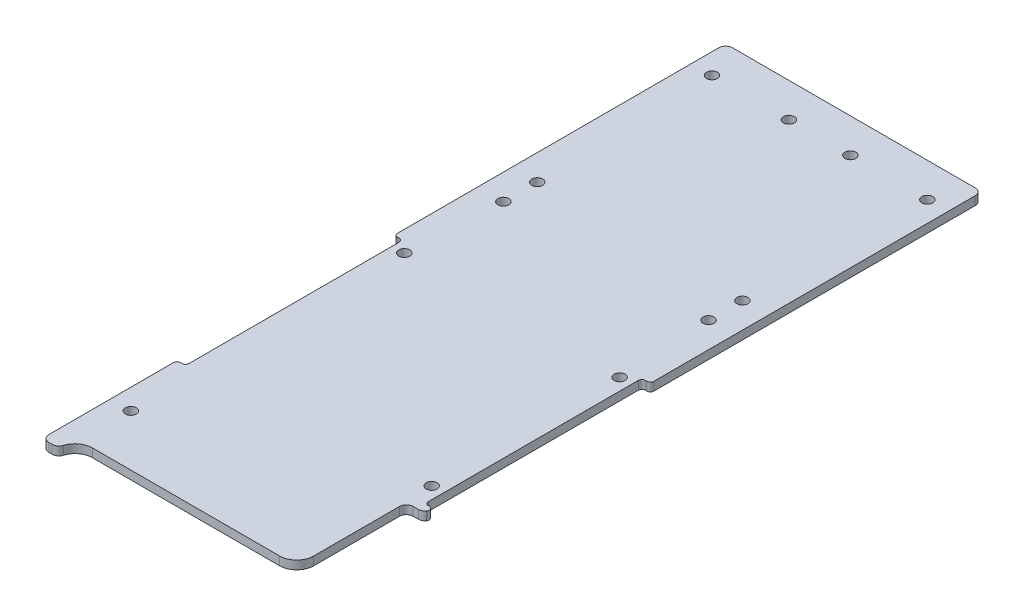
SolidWorks part; units mm, degrees
ref_plane "Front Plane" through (0, 0, 0) normal (0, 0, 1) x (1, 0, 0)
ref_plane "Top Plane" through (0, 0, 0) normal (0, 1, 0) x (1, 0, 0)
ref_plane "Right Plane" through (0, 0, 0) normal (1, 0, 0) x (0, 0, -1)
sketch "Sketch1" plane through (0, 0, 0) normal (0, 1, 0) x (1, 0, 0)
  line L0 (-39.9997, 0) -> (-39.9997, 114.3) construction
  line L1 (-47.625, 127) -> (47.625, 127)
  line L2 (-47.625, 127) -> (-47.625, -127)
  line L3 (-47.625, -127) -> (47.625, -127)
  line L4 (47.625, 127) -> (47.625, -127)
  line L5 (-47.625, 127) -> (47.625, -127) construction
  line L6 (-47.625, -127) -> (47.625, 127) construction
  line L7 (0, 0) -> (0, 127) construction
  line L8 (-39.9997, 0) -> (-39.9997, -101.6) construction
  line L9 (-39.9997, 0) -> (0, 0) construction
  line L10 (-41.275, -127) -> (-41.275, -120.65)
  line L11 (-41.275, -120.65) -> (41.275, -120.65)
  line L12 (41.275, -120.65) -> (41.275, -127)
  line L13 (-39.9997, 114.3) -> (-11.4247, 114.3) construction
  line L14 (39.9997, 114.3) -> (11.4247, 114.3) construction
  circle A0 centre (-39.9997, 114.3) radius 2.032
  circle A1 centre (-39.9997, 0) radius 2.032
  circle A2 centre (-39.9997, -101.6) radius 2.032
  circle A3 centre (39.9997, -101.6) radius 2.032
  circle A4 centre (39.9997, 0) radius 2.032
  circle A5 centre (39.9997, 114.3) radius 2.032
  circle A6 centre (-11.4247, 114.3) radius 2.032
  circle A7 centre (11.4247, 114.3) radius 2.032
  circle A8 centre (-39.9997, -69.85) radius 2.032
  circle A9 centre (39.9997, -69.85) radius 2.032
  point P0 (0, 0)
  dimension "D4" = 4.064
  dimension "D10" = 28.575
  dimension "D1" = 95.25
  dimension "D2" = 254
  dimension "D3" = 7.6253
  dimension "D5" = 12.7
  dimension "D6" = 25.4
  dimension "D7" = 6.35
  dimension "D8" = 6.35
  dimension "D9" = 6.35
  dimension "D11" = 69.85
extrude "Boss-Extrude1" add sketch "Sketch1" along normal blind 3.175 contours L4 L1 L2 L3 A4 A0 A1 A2 A3 A5 | A8 | A3 region at (0, 0, -2.6944) region at (39.9997, 0, 101.6) region at (-39.9997, 0, 69.85)
fillet "Fillet1" radius 2.54 4 edges at (-47.625, 1.5875, -127) (47.625, 1.5875, -127) (47.625, 1.5875, 127) (-47.625, 1.5875, 127)
fillet "Fillet2" radius 2.54 2 edges at (41.275, 1.5875, 127) (-41.275, 1.5875, 127)
fillet "Fillet3" radius 6.35 2 edges at (41.275, 1.5875, 120.65) (-41.275, 1.5875, 120.65)
sketch "Sketch2" plane through (0, 0, 0) normal (0, -1, 0) x (1, 0, 0)
  line L1 (43.815, 127) -> (45.085, 127) construction
  line L2 (40.6451, 123.5787) -> (40.6451, 79.8881)
  line L3 (40.6451, 79.8881) -> (47.625, 79.8881)
  line L11 (47.625, -124.46) -> (47.625, 124.46) construction
  line L12 (43.815, 127) -> (45.085, 127)
  line L13 (47.625, 79.8881) -> (47.625, 124.46)
  arc A0 (35.2956, 120.65) -> (41.3809, 125.1857) centre (35.2956, 127) ccw construction
  arc A1 (43.815, 127) -> (41.3809, 125.1857) centre (43.815, 124.46) ccw construction
  arc A2 (47.625, 124.46) -> (45.085, 127) centre (45.085, 124.46) ccw construction
  arc A3 (40.6451, 123.5787) -> (41.3809, 125.1857) centre (35.2956, 127) ccw
  arc A4 (43.815, 127) -> (41.3809, 125.1857) centre (43.815, 124.46) ccw
  arc A5 (47.625, 124.46) -> (45.085, 127) centre (45.085, 124.46) ccw
  dimension "D2" = 47.1119
  dimension "D1" = 6.9799
extrude "Cut-Extrude1" cut sketch "Sketch2" against normal through all
fillet "Fillet4" radius 6.35 1 edges at (40.6451, 1.5875, 123.5787)
fillet "Fillet5" radius 2.54 2 edges at (47.625, 1.5875, 79.8881) (40.6451, 1.5875, 79.8881)
sketch "Sketch3" plane through (0, 0, 0) normal (0, -1, 0) x (1, 0, 0)
  line L0 (-36.3007, -49.7791) -> (-39.9075, -49.7791) construction
  line L1 (-40.4155, -49.276) -> (-40.4155, -45.7043) construction
  line L2 (-35.7927, -45.7043) -> (-35.7927, -49.276) construction
  line L3 (-39.9075, -45.2013) -> (-36.3007, -45.2013) construction
  line L4 (-36.3007, -37.2027) -> (-39.9075, -37.2027) construction
  line L5 (-35.7927, -33.1279) -> (-35.7927, -36.6996) construction
  line L6 (-40.4155, -36.6996) -> (-40.4155, -33.1279) construction
  line L7 (-39.9075, -32.6249) -> (-36.3007, -32.6249) construction
  line L8 (36.2925, -32.6249) -> (39.8993, -32.6249) construction
  line L9 (40.4073, -33.1279) -> (40.4073, -36.6996) construction
  line L10 (39.8993, -37.2027) -> (36.2925, -37.2027) construction
  line L11 (35.7845, -36.6996) -> (35.7845, -33.1279) construction
  line L12 (36.2925, -45.2013) -> (39.8993, -45.2013) construction
  line L13 (35.7845, -49.276) -> (35.7845, -45.7043) construction
  line L14 (40.4073, -45.7043) -> (40.4073, -49.276) construction
  line L15 (39.8993, -49.7791) -> (36.2925, -49.7791) construction
  line L16 (-36.3007, -49.7791) -> (-39.9075, -49.7791)
  line L17 (-40.4155, -49.276) -> (-40.4155, -45.7043)
  line L18 (-35.7927, -45.7043) -> (-35.7927, -49.276)
  line L19 (-39.9075, -45.2013) -> (-36.3007, -45.2013)
  line L20 (-36.3007, -37.2027) -> (-39.9075, -37.2027)
  line L21 (-35.7927, -33.1279) -> (-35.7927, -36.6996)
  line L22 (-40.4155, -36.6996) -> (-40.4155, -33.1279)
  line L23 (-39.9075, -32.6249) -> (-36.3007, -32.6249)
  line L24 (36.2925, -32.6249) -> (39.8993, -32.6249)
  line L25 (40.4073, -33.1279) -> (40.4073, -36.6996)
  line L26 (39.8993, -37.2027) -> (36.2925, -37.2027)
  line L27 (35.7845, -36.6996) -> (35.7845, -33.1279)
  line L28 (36.2925, -45.2013) -> (39.8993, -45.2013)
  line L29 (35.7845, -49.276) -> (35.7845, -45.7043)
  line L30 (40.4073, -45.7043) -> (40.4073, -49.276)
  line L31 (39.8993, -49.7791) -> (36.2925, -49.7791)
  line L32 (-47.625, -25.836) -> (47.625, -25.836)
  line L33 (-47.625, -124.46) -> (-47.625, 124.46) construction
  line L34 (47.625, -124.46) -> (47.625, 77.3481) construction
  line L35 (0, -25.836) -> (0, -56.0686) construction
  line L1362 (-40.4155, -34.9138) -> (-35.7927, -34.9138)
  line L1857 (-38.1041, -32.6249) -> (-38.1041, -37.2027)
  line L1858 (-38.1041, -45.2013) -> (-38.1041, -49.7791)
  line L1859 (-40.4155, -47.4902) -> (-35.7927, -47.4902)
  circle A0 centre (-38.1041, -34.9138) radius 2.032
  circle A1 centre (-38.1041, -47.4902) radius 2.032
  circle A2 centre (38.1041, -47.4902) radius 2.032
  circle A3 centre (38.1041, -34.9138) radius 2.032
  ellipse E0 centre (-39.9075, -45.7043) end of major axis (-39.3995, -45.7043) minor radius 0.5031 (-39.9075, -45.2013) -> (-40.4155, -45.7043) ccw construction
  ellipse E1 centre (-39.9075, -49.276) end of major axis (-39.3995, -49.276) minor radius 0.5031 (-40.4155, -49.276) -> (-39.9075, -49.7791) ccw construction
  ellipse E6 centre (-36.3007, -49.276) end of major axis (-35.7927, -49.276) minor radius 0.5031 (-36.3007, -49.7791) -> (-35.7927, -49.276) ccw construction
  ellipse E7 centre (-36.3007, -45.7043) end of major axis (-35.7927, -45.7043) minor radius 0.5031 (-35.7927, -45.7043) -> (-36.3007, -45.2013) ccw construction
  ellipse E8 centre (-39.9075, -36.6996) end of major axis (-39.3995, -36.6996) minor radius 0.5031 (-40.4155, -36.6996) -> (-39.9075, -37.2027) ccw construction
  ellipse E9 centre (-36.3007, -36.6996) end of major axis (-35.7927, -36.6996) minor radius 0.5031 (-36.3007, -37.2027) -> (-35.7927, -36.6996) ccw construction
  ellipse E10 centre (-36.3007, -33.1279) end of major axis (-35.7927, -33.1279) minor radius 0.5031 (-35.7927, -33.1279) -> (-36.3007, -32.6249) ccw construction
  ellipse E11 centre (-39.9075, -33.1279) end of major axis (-39.3995, -33.1279) minor radius 0.5031 (-39.9075, -32.6249) -> (-40.4155, -33.1279) ccw construction
  ellipse E12 centre (39.8993, -33.1279) end of major axis (40.4073, -33.1279) minor radius 0.5031 (40.4073, -33.1279) -> (39.8993, -32.6249) ccw construction
  ellipse E13 centre (36.2925, -33.1279) end of major axis (36.8005, -33.1279) minor radius 0.5031 (36.2925, -32.6249) -> (35.7845, -33.1279) ccw construction
  ellipse E14 centre (39.8993, -36.6996) end of major axis (40.4073, -36.6996) minor radius 0.5031 (39.8993, -37.2027) -> (40.4073, -36.6996) ccw construction
  ellipse E15 centre (36.2925, -36.6996) end of major axis (36.8005, -36.6996) minor radius 0.5031 (35.7845, -36.6996) -> (36.2925, -37.2027) ccw construction
  ellipse E16 centre (36.2925, -45.7043) end of major axis (36.8005, -45.7043) minor radius 0.5031 (36.2925, -45.2013) -> (35.7845, -45.7043) ccw construction
  ellipse E17 centre (36.2925, -49.276) end of major axis (36.8005, -49.276) minor radius 0.5031 (35.7845, -49.276) -> (36.2925, -49.7791) ccw construction
  ellipse E18 centre (39.8993, -45.7043) end of major axis (40.4073, -45.7043) minor radius 0.5031 (40.4073, -45.7043) -> (39.8993, -45.2013) ccw construction
  ellipse E19 centre (39.8993, -49.276) end of major axis (40.4073, -49.276) minor radius 0.5031 (39.8993, -49.7791) -> (40.4073, -49.276) ccw construction
  ellipse E20 centre (-39.9075, -45.7043) end of major axis (-39.3995, -45.7043) minor radius 0.5031 (-39.9075, -45.2013) -> (-40.4155, -45.7043) ccw
  ellipse E21 centre (-39.9075, -49.276) end of major axis (-39.3995, -49.276) minor radius 0.5031 (-40.4155, -49.276) -> (-39.9075, -49.7791) ccw
  ellipse E22 centre (-36.3007, -49.276) end of major axis (-35.7927, -49.276) minor radius 0.5031 (-36.3007, -49.7791) -> (-35.7927, -49.276) ccw
  ellipse E23 centre (-36.3007, -45.7043) end of major axis (-35.7927, -45.7043) minor radius 0.5031 (-35.7927, -45.7043) -> (-36.3007, -45.2013) ccw
  ellipse E24 centre (-39.9075, -36.6996) end of major axis (-39.3995, -36.6996) minor radius 0.5031 (-40.4155, -36.6996) -> (-39.9075, -37.2027) ccw
  ellipse E25 centre (-36.3007, -36.6996) end of major axis (-35.7927, -36.6996) minor radius 0.5031 (-36.3007, -37.2027) -> (-35.7927, -36.6996) ccw
  ellipse E26 centre (-36.3007, -33.1279) end of major axis (-35.7927, -33.1279) minor radius 0.5031 (-35.7927, -33.1279) -> (-36.3007, -32.6249) ccw
  ellipse E27 centre (-39.9075, -33.1279) end of major axis (-39.3995, -33.1279) minor radius 0.5031 (-39.9075, -32.6249) -> (-40.4155, -33.1279) ccw
  ellipse E28 centre (39.8993, -33.1279) end of major axis (40.4073, -33.1279) minor radius 0.5031 (40.4073, -33.1279) -> (39.8993, -32.6249) ccw
  ellipse E29 centre (36.2925, -33.1279) end of major axis (36.8005, -33.1279) minor radius 0.5031 (36.2925, -32.6249) -> (35.7845, -33.1279) ccw
  ellipse E30 centre (39.8993, -36.6996) end of major axis (40.4073, -36.6996) minor radius 0.5031 (39.8993, -37.2027) -> (40.4073, -36.6996) ccw
  ellipse E31 centre (36.2925, -36.6996) end of major axis (36.8005, -36.6996) minor radius 0.5031 (35.7845, -36.6996) -> (36.2925, -37.2027) ccw
  ellipse E32 centre (36.2925, -45.7043) end of major axis (36.8005, -45.7043) minor radius 0.5031 (36.2925, -45.2013) -> (35.7845, -45.7043) ccw
  ellipse E33 centre (36.2925, -49.276) end of major axis (36.8005, -49.276) minor radius 0.5031 (35.7845, -49.276) -> (36.2925, -49.7791) ccw
  ellipse E34 centre (39.8993, -45.7043) end of major axis (40.4073, -45.7043) minor radius 0.5031 (40.4073, -45.7043) -> (39.8993, -45.2013) ccw
  ellipse E35 centre (39.8993, -49.276) end of major axis (40.4073, -49.276) minor radius 0.5031 (39.8993, -49.7791) -> (40.4073, -49.276) ccw
  dimension "D2" = 4.064
extrude "Cut-Extrude2" cut sketch "Sketch3" against normal through all contours A0 | A1 | A2 | A3
sketch "Sketch4" plane through (0, 3.175, 0) normal (0, 1, 0) x (1, 0, 0)
  line L11 (-47.625, 124.46) -> (-47.625, -124.46) construction
  line L12 (-47.625, -76.835) -> (-44.45, -76.835)
  line L13 (-47.625, -76.835) -> (-47.625, 3.81)
  line L15 (-47.625, 3.81) -> (-44.45, 3.81)
  line L16 (-44.45, -76.835) -> (-44.45, 3.81)
  line L17 (47.625, 124.46) -> (47.625, -77.3481) construction
  line L18 (47.625, -76.835) -> (44.45, -76.835)
  line L19 (47.625, -76.835) -> (47.625, 3.81)
  line L20 (47.625, 3.81) -> (44.45, 3.81)
  line L45 (44.45, -76.835) -> (44.45, 3.81)
  line L47 (43.1851, -79.8881) -> (45.085, -79.8881) construction
  dimension "D1" = 3.175
  dimension "D2" = 80.645
  dimension "D3" = 3.0531
extrude "Cut-Extrude3" cut sketch "Sketch4" against normal through all and the other way through all
fillet "Fillet6" radius 1.27 8 edges at (-44.45, 1.5875, -3.81) (-47.625, 1.5875, -3.81) (-47.625, 1.5875, 76.835) (-44.45, 1.5875, 76.835) (44.45, 1.5875, 76.835) (47.625, 1.5875, 76.835) (44.45, 1.5875, -3.81) (47.625, 1.5875, -3.81)
